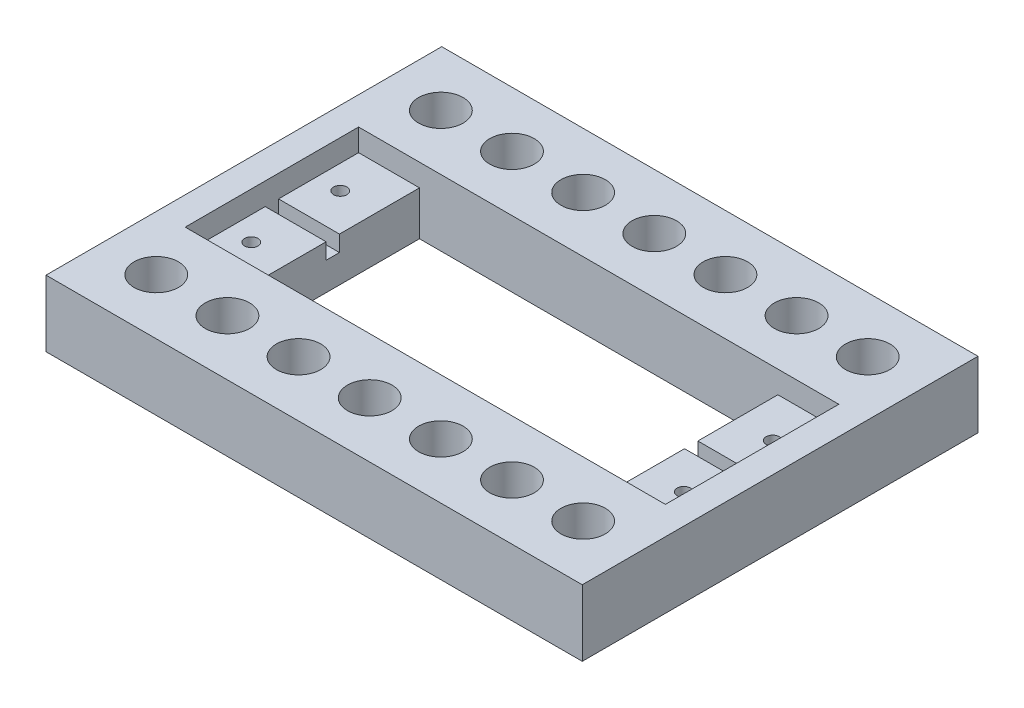
SolidWorks part; units mm, degrees
ref_plane "Front Plane" through (0, 0, 0) normal (0, 0, 1) x (1, 0, 0)
ref_plane "Top Plane" through (0, 0, 0) normal (0, 1, 0) x (1, 0, 0)
ref_plane "Right Plane" through (0, 0, 0) normal (1, 0, 0) x (0, 0, -1)
sketch "Sketch1" plane through (0, 0, 0) normal (0, 1, 0) x (1, 0, 0)
  line L0 (-34.3973, 0) -> (32.9918, 0) construction
  line L1 (-20.15, 9.75) -> (20.15, 9.75)
  line L2 (-20.15, 9.75) -> (-20.15, -9.75)
  line L3 (-20.15, -9.75) -> (20.15, -9.75)
  line L4 (20.15, 9.75) -> (20.15, -9.75)
  line L5 (-20.15, 9.75) -> (20.15, -9.75) construction
  line L6 (-20.15, -9.75) -> (20.15, 9.75) construction
  line L7 (0, 26.5192) -> (0, -28.2205) construction
  line L9 (-30.15, 22.25) -> (30.15, 22.25)
  line L10 (-30.15, 22.25) -> (-30.15, -22.25)
  line L11 (-30.15, -22.25) -> (30.15, -22.25)
  line L12 (30.15, 22.25) -> (30.15, -22.25)
  line L13 (-27, 9.75) -> (27, 9.75) construction
  line L14 (-27, 9.75) -> (-27, -9.75) construction
  line L15 (-27, -9.75) -> (27, -9.75) construction
  line L16 (27, 9.75) -> (27, -9.75) construction
  line L17 (-27, 9.75) -> (27, -9.75) construction
  line L18 (-27, -9.75) -> (27, 9.75) construction
  circle A0 centre (-24.315, -5) radius 0.75
  circle A1 centre (-24.315, 5) radius 0.75
  circle A2 centre (24.315, -5) radius 0.75
  circle A3 centre (24.315, 5) radius 0.75
  point P0 (0, 0)
  point P14 (0, 0)
  dimension "D9" = 24.315
  dimension "D8" = 1.5
  dimension "D10" = 5
  dimension "D1" = 40.3
  dimension "D2" = 19.5
  dimension "D3" = 12.5
  dimension "D4" = 12.5
  dimension "D5" = 10
  dimension "D6" = 10
  dimension "D7" = 54
extrude "Boss-Extrude1" add sketch "Sketch1" along normal blind 7.46
sketch "Sketch3" plane through (0, 7.46, 0) normal (0, 1, 0) x (1, 0, 0)
  line L1 (-27, 9.75) -> (27, 9.75)
  line L2 (-27, 9.75) -> (-27, -9.75)
  line L3 (-27, -9.75) -> (27, -9.75)
  line L4 (27, 9.75) -> (27, -9.75)
  line L5 (-27, 9.75) -> (27, -9.75) construction
  line L6 (-27, -9.75) -> (27, 9.75) construction
  point P0 (0, 0)
  dimension "D1" = 19.5
  dimension "D2" = 54
extrude "Cut-Extrude1" cut sketch "Sketch3" against normal blind 2.5
sketch "Sketch4" plane through (0, 7.46, 0) normal (0, 1, 0) x (1, 0, 0)
  line L0 (0, 22.25) -> (0, 9.75) construction
  line L1 (30.15, 22.25) -> (-30.15, 22.25) construction
  line L2 (27, 9.75) -> (-27, 9.75) construction
  line L3 (0, 16) -> (-30.15, 16) construction
  line L4 (-30.15, 22.25) -> (-30.15, -22.25) construction
  line L5 (-20.15, 0) -> (20.15, 0) construction
  line L6 (-20.15, 9.75) -> (-20.15, -9.75) construction
  line L7 (20.15, -9.75) -> (20.15, 9.75) construction
  circle A0 centre (0, 16) radius 2.5
  circle A1 centre (8, 16) radius 2.5
  circle A2 centre (16, 16) radius 2.5
  circle A3 centre (24, 16) radius 2.5
  circle A4 centre (-24, 16) radius 2.5
  circle A5 centre (-16, 16) radius 2.5
  circle A6 centre (-8, 16) radius 2.5
  circle A7 centre (24, -16) radius 2.5
  circle A8 centre (16, -16) radius 2.5
  circle A9 centre (8, -16) radius 2.5
  circle A10 centre (0, -16) radius 2.5
  circle A11 centre (-8, -16) radius 2.5
  circle A12 centre (-16, -16) radius 2.5
  circle A13 centre (-24, -16) radius 2.5
  dimension "D1" = 5
  dimension "D3" = 8
  dimension "D2" = 4
extrude "Cut-Extrude2" cut sketch "Sketch4" against normal through all
sketch "Sketch5" plane through (0, 4.96, 0) normal (0, 1, 0) x (1, 0, 0)
  line L0 (-27, 0) -> (27, 0) construction
  line L1 (-27, 9.75) -> (-27, -9.75) construction
  line L2 (27, -9.75) -> (27, 9.75) construction
  line L3 (-27, -0.75) -> (-20.15, -0.75)
  line L4 (-20.15, 9.75) -> (-20.15, -9.75) construction
  line L5 (-27, 0.75) -> (-20.15, 0.75)
  line L6 (-27, -0.75) -> (-27, 0.75)
  line L7 (-20.15, -0.75) -> (-20.15, 0.75)
  line L8 (0, 0) -> (0, -25.0299) construction
  line L9 (20.15, -0.75) -> (20.15, 0.75)
  line L10 (27, 0.75) -> (20.15, 0.75)
  line L11 (27, -0.75) -> (20.15, -0.75)
  line L12 (27, -0.75) -> (27, 0.75)
  dimension "D1" = 1.5
extrude "Cut-Extrude3" cut sketch "Sketch5" against normal blind 1.8
